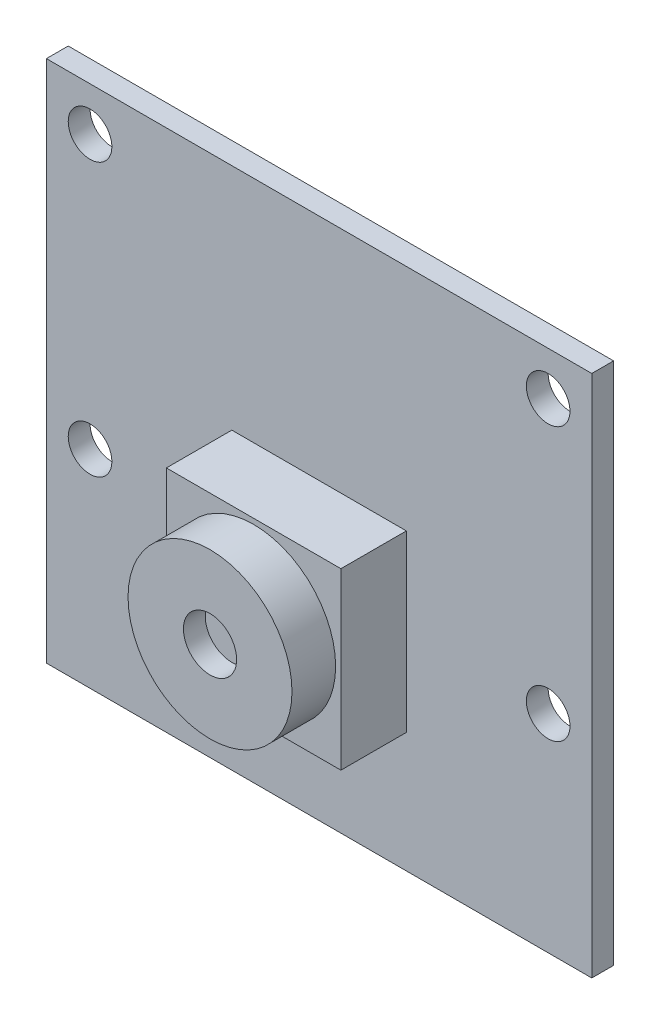
SolidWorks part; units mm, degrees
ref_plane "Front Plane" through (0, 0, 0) normal (0, 0, 1) x (1, 0, 0)
ref_plane "Top Plane" through (0, 0, 0) normal (0, 1, 0) x (1, 0, 0)
ref_plane "Right Plane" through (0, 0, 0) normal (1, 0, 0) x (0, 0, -1)
ref_axis "Axis1" through (-88.99, 0, 0) along (1, 0, 0)
ref_axis "Axis2" through (0, 55, 0) along (0, -1, 0)
ref_axis "Axis3" through (0, 0, 55) along (0, 0, -1)
ref_point "Point1"
sketch "Sketch1" plane through (0, 0, 0) normal (0, 0, 1) x (1, 0, 0)
  line L1 (-12.5, -12) -> (12.5, -12)
  line L2 (-12.5, -12) -> (-12.5, 12)
  line L3 (-12.5, 12) -> (12.5, 12)
  line L4 (12.5, -12) -> (12.5, 12)
  line L5 (-12.5, -12) -> (12.5, 12) construction
  line L6 (-12.5, 12) -> (12.5, -12) construction
  point P0 (0, 0)
  dimension "D1" = 25
  dimension "D2" = 24
extrude "Boss-Extrude1" add sketch "Sketch1" along normal blind 1
sketch "Sketch2" plane through (0, 0, 1) normal (0, 0, 1) x (1, 0, 0)
  line L0 (-12.5, -12) -> (12.5, -12) construction
  line L1 (-4, -6.5) -> (4, -6.5)
  line L2 (-4, -6.5) -> (-4, 1.5)
  line L3 (-4, 1.5) -> (4, 1.5)
  line L4 (4, -6.5) -> (4, 1.5)
  line L5 (-4, -6.5) -> (4, 1.5) construction
  line L6 (-4, 1.5) -> (4, -6.5) construction
  line L7 (-12.5, 12) -> (-12.5, -12) construction
  point P0 (0, -2.5)
  dimension "D1" = 8
  dimension "D2" = 5.5
  dimension "D3" = 8.5
extrude "Boss-Extrude2" add sketch "Sketch2" along normal blind 3 separate body
sketch "Sketch3" plane through (0, 0, 4) normal (0, 0, 1) x (1, 0, 0)
  line L0 (-4, -6.5) -> (4, 1.5) construction
  line L1 (4, -6.5) -> (4, 1.5) construction
  line L2 (4, 1.5) -> (-4, 1.5) construction
  circle A0 centre (0, -2.5) radius 3.7578
extrude "Boss-Extrude3" add sketch "Sketch3" along normal blind 2 separate body
sketch "Sketch4" plane through (0, 0, 6) normal (0, 0, 1) x (1, 0, 0)
  circle A0 centre (0, -2.5) radius 1.219
extrude "Cut-Extrude1" cut sketch "Sketch4" against normal blind 1
sketch "Sketch5" plane through (0, 0, 1) normal (0, 0, 1) x (1, 0, 0)
  line L0 (-12.5, -12) -> (12.5, -12) construction
  line L1 (-10.5, 10) -> (10.5, 10) construction
  line L2 (-10.5, 10) -> (-10.5, -2.5) construction
  line L3 (-10.5, -2.5) -> (10.5, -2.5) construction
  line L4 (10.5, 10) -> (10.5, -2.5) construction
  line L5 (-10.5, 10) -> (10.5, -2.5) construction
  line L6 (-10.5, -2.5) -> (10.5, 10) construction
  line L7 (12.5, 12) -> (-12.5, 12) construction
  line L8 (0, 10) -> (0, 12) construction
  circle A0 centre (-10.5, -2.5) radius 1
  circle A1 centre (-10.5, 10) radius 1
  circle A2 centre (10.5, 10) radius 1
  circle A3 centre (10.5, -2.5) radius 1
  point P0 (0, 3.75)
  dimension "D4" = 2
  dimension "D1" = 9.5
  dimension "D2" = 2
  dimension "D3" = 21
extrude "Cut-Extrude2" cut sketch "Sketch5" against normal through all both and the other way through all
